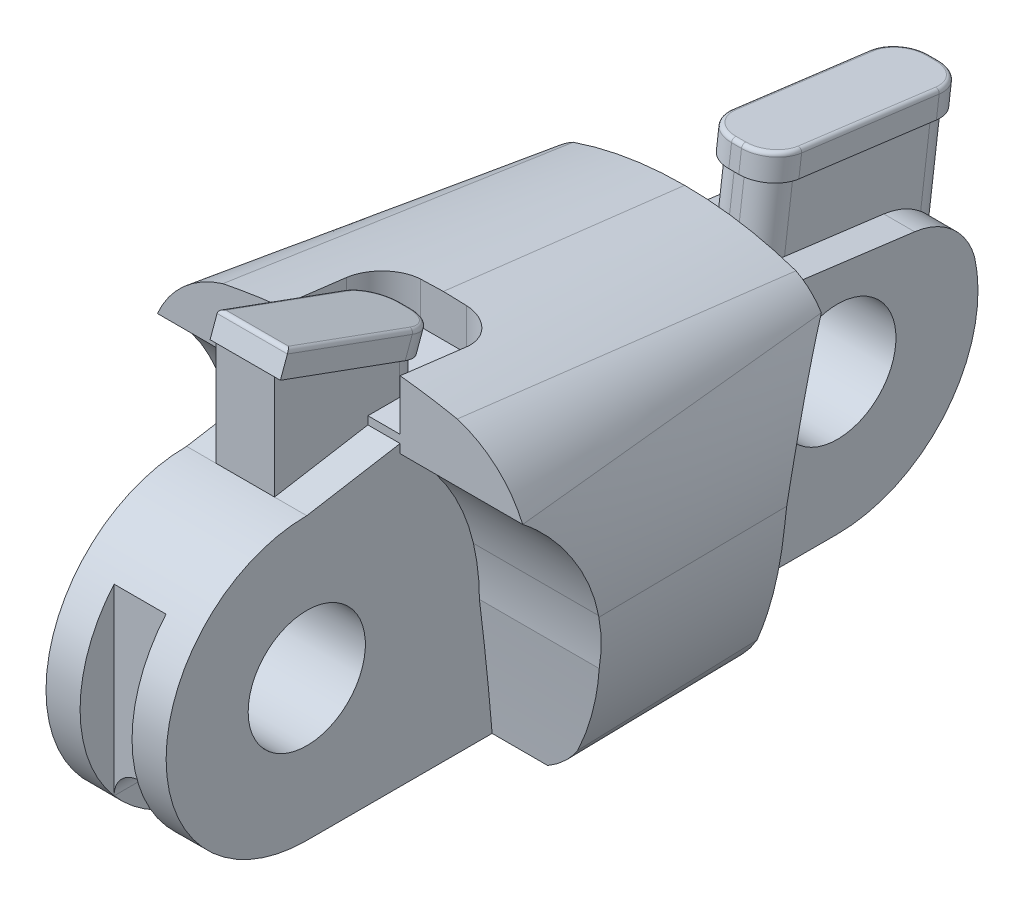
SolidWorks part; units mm, degrees
material "PET"
ref_plane "Front Plane" through (0, 0, 0) normal (0, 0, 1) x (1, 0, 0)
ref_plane "Top Plane" through (0, 0, 0) normal (0, 1, 0) x (1, 0, 0)
ref_plane "Right Plane" through (0, 0, 0) normal (1, 0, 0) x (0, 0, -1)
sketch "Sketch1" plane through (0, 0, 0) normal (1, 0, 0) x (0, 0, -1)
  line L0 (-17.2498, 0) -> (17.2498, 0) construction
  line L1 (-17.2498, 9.144) -> (17.2498, 9.144)
  line L2 (-17.2498, -9.144) -> (17.2498, -9.144)
  arc A0 (-17.2498, 9.144) -> (-17.2498, -9.144) centre (-17.2498, 0) ccw
  arc A1 (17.2498, -9.144) -> (17.2498, 9.144) centre (17.2498, 0) ccw
  circle A2 centre (-17.2498, 0) radius 3.81
  circle A3 centre (17.2498, 0) radius 3.81
  point P3 (0, 0)
  dimension "D2" = 9.144
  dimension "D3" = 7.62
  dimension "D1" = 34.4995
extrude "Boss-Extrude1" add sketch "Sketch1" along normal mid plane 7.8105
ref_plane "Plane1" through (0, 0, 11.1792) normal (0, 0, 1) x (1, 0, 0)
ref_plane "Plane2" through (0, 0, -11.2236) normal (0, 0, 1) x (1, 0, 0)
sketch "Sketch2" plane through (0, 0, 11.1792) normal (0, 0, 1) x (1, 0, 0)
  line L0 (0, -9.144) -> (0, 13.716) construction
  line L1 (3.9052, -9.144) -> (-3.9052, -9.144) construction
  line L2 (3.9053, 13.716) -> (-3.9053, 13.716) construction
  line L3 (7.62, -9.144) -> (-7.62, -9.144)
  line L4 (0, 2.286) -> (-12.319, 2.286) construction
  line L5 (0, 9.6012) -> (-11.8745, 9.6012) construction
  line L6 (-3.9052, 9.144) -> (-3.9052, -9.144) construction
  arc A0 (-7.62, -9.144) -> (-9.652, -7.3279) centre (-4.2348, -3.3115) cw
  arc A1 (-12.319, 2.286) -> (-9.652, -7.3279) centre (9.1301, 3.0593) ccw
  arc A2 (-12.319, 2.286) -> (-11.8745, 9.6012) centre (16.3435, 4.2155) cw
  arc A3 (-11.8745, 9.6012) -> (-7.62, 13.4112) centre (-5.6343, 6.9134) cw
  arc A4 (-7.62, 13.4112) -> (0, 14.224) centre (0.4948, -26.54) cw
  arc A5 (7.62, -9.144) -> (9.652, -7.3279) centre (4.2348, -3.3115) ccw
  arc A6 (12.319, 2.286) -> (9.652, -7.3279) centre (-9.1301, 3.0593) cw
  arc A7 (12.319, 2.286) -> (11.8745, 9.6012) centre (-16.3435, 4.2155) ccw
  arc A8 (11.8745, 9.6012) -> (7.62, 13.4112) centre (5.6343, 6.9134) ccw
  arc A9 (7.62, 13.4112) -> (0, 14.224) centre (-0.4948, -26.54) ccw
  dimension "D6" = 6.7437
  dimension "D9" = 21.463
  dimension "D10" = 28.7274
  dimension "D12" = 6.7945
  dimension "D14" = 40.767
  dimension "D1" = 22.86
  dimension "D2" = 7.62
  dimension "D3" = 12.319
  dimension "D4" = 11.8745
  dimension "D5" = 7.3152
  dimension "D7" = 2.032
  dimension "D8" = 1.8161
  dimension "D11" = 3.81
  dimension "D13" = 0.508
sketch "Sketch3" plane through (0, 0, -11.2236) normal (0, 0, 1) x (1, 0, 0)
  line L0 (0, -9.144) -> (0, 11.557) construction
  line L1 (3.9052, -9.144) -> (-3.9052, -9.144) construction
  line L2 (7.239, -9.144) -> (-7.239, -9.144)
  line L3 (0, 1.2065) -> (-10.9855, 1.2065) construction
  line L4 (0, 8.8265) -> (-8.89, 8.8265) construction
  line L5 (164.5619, 543.9025) -> (873.8952, 543.9025) construction
  arc A0 (-7.239, -9.144) -> (-9.6266, -6.604) centre (-3.4088, -3.1515) cw
  arc A1 (-9.6266, -6.604) -> (-10.9855, 1.2065) centre (7.283, 0.3615) cw
  arc A2 (-10.9855, 1.2065) -> (-8.89, 8.8265) centre (3.2373, 1.3934) cw
  arc A3 (-8.89, 8.8265) -> (-7.239, 10.3632) centre (-5.303, 6.6279) cw
  arc A4 (-7.239, 10.3632) -> (0, 11.557) centre (-0.0528, -10.6679) cw
  arc A5 (7.239, -9.144) -> (9.6266, -6.604) centre (3.4088, -3.1515) ccw
  arc A6 (9.6266, -6.604) -> (10.9855, 1.2065) centre (-7.283, 0.3615) ccw
  arc A7 (10.9855, 1.2065) -> (8.89, 8.8265) centre (-3.2373, 1.3934) ccw
  arc A8 (8.89, 8.8265) -> (7.239, 10.3632) centre (5.303, 6.6279) ccw
  arc A9 (7.239, 10.3632) -> (0, 11.557) centre (0.0528, -10.6679) ccw
  point P10 (0, 1.2065)
  dimension "D6" = 7.112
  dimension "D9" = 18.288
  dimension "D10" = 14.224
  dimension "D12" = 22.225
  dimension "D1" = 20.701
  dimension "D2" = 7.239
  dimension "D3" = 10.9855
  dimension "D4" = 8.89
  dimension "D5" = 7.62
  dimension "D7" = 2.54
  dimension "D8" = 2.3876
  dimension "D11" = 1.5367
loft "Loft1" add profiles "Sketch2", "Sketch3" connector at (0, 14.224, 11.1792) connector at (0, 11.557, -11.2236)
sketch "Sketch5" plane through (-3.9052, 0, 0) normal (-1, 0, 0) x (0, 0, 1)
  line L0 (11.1792, 9.6012) -> (11.1792, -9.144)
  line L1 (17.2498, -9.144) -> (-17.2498, -9.144) construction
  line L2 (11.1792, -9.144) -> (5.1975, -9.144)
  line L3 (11.1792, -9.144) -> (-11.2236, -9.144) construction
  line L4 (11.1792, 2.286) -> (11.1792, 9.6012) construction
  line L5 (-11.2236, 8.8265) -> (-11.2236, -9.144)
  line L6 (-11.2236, -9.144) -> (-6.4611, -9.144)
  line L7 (91.3421, 313.5507) -> (503.3421, 313.5507) construction
  arc A0 (11.1792, 9.6012) -> (6.4141, 2.1704) centre (19.294, -0.8457) ccw
  arc A1 (6.4141, 2.1704) -> (6.023, -1.1824) centre (20.8747, -1.2159) ccw
  arc A2 (5.1975, -9.144) -> (6.023, -1.1824) centre (199.298, -25.2457) cw
  arc A3 (-11.2236, 8.8265) -> (-6.4611, 0.4026) centre (-18.1635, -0.6552) cw
  arc A4 (-6.4611, 0.4026) -> (-6.4611, -9.144) centre (-59.2693, -4.3707) cw
  dimension "D3" = 13.2283
  dimension "D8" = 194.7672
  dimension "D9" = 11.75
  dimension "D1" = 5.9817
  dimension "D2" = 4.7625
  dimension "D4" = 4.765
  dimension "D5" = 7.4308
  dimension "D6" = 5.1562
  dimension "D7" = 3.3528
  dimension "D10" = 8.4239
extrude "Cut-Extrude1" cut sketch "Sketch5" along normal blind 10.16
mirror "Mirror1" about plane through (0, 0, 0) normal (1, 0, 0) of "Cut-Extrude1"
sketch "Sketch6" plane through (-3.9052, 0, 0) normal (-1, 0, 0) x (0, 0, 1)
  line L0 (-11.2236, 11.5571) -> (-11.2236, -9.144) construction
  line L1 (17.2498, -9.144) -> (-17.2498, -9.144) construction
  line L2 (-11.2236, 8.8265) -> (-11.2236, -9.144) construction
  line L3 (0, 0) -> (-26.3938, 0) construction
  line L4 (54.4978, 392.9909) -> (430.4978, 392.9909) construction
  line L5 (141.4324, 674.1494) -> (813.4324, 674.1494) construction
  line L6 (-11.2236, 11.5571) -> (-11.2236, 2.0067) construction
  line L7 (-11.2236, 2.0067) -> (-26.1709, 2.0067) construction
  line L8 (-11.2236, 6.7946) -> (-22.2726, 5.3713)
  line L9 (-26.1709, 2.0067) -> (-26.1709, 11.5571)
  line L10 (-26.1709, 11.5571) -> (-11.2236, 11.5571)
  line L11 (-11.2236, 11.5571) -> (-11.2236, 6.7946)
  arc A0 (-17.2498, 9.144) -> (-17.2498, -9.144) centre (-17.2498, 0) ccw construction
  arc A1 (-26.1709, 2.0067) -> (-22.2726, 5.3713) centre (-21.676, 0.7395) cw
  dimension "D1" = 9.5504
  dimension "D2" = 4.7879
  dimension "D3" = 97.34
  dimension "D4" = 11.049
extrude "Cut-Extrude2" cut sketch "Sketch6" against normal up to surface (7.8105 mm away) up to face at (3.9052, 0, 13.4398)
sketch "Sketch7" plane through (0, 9.144, 0) normal (0, 1, 0) x (1, 0, 0)
  line L0 (-3.9052, -11.1792) -> (3.9052, -11.1792)
  line L1 (-3.9052, 11.2236) -> (-3.9052, -17.2498) construction
  line L2 (3.9052, 11.2236) -> (3.9052, -17.2498) construction
  line L3 (-3.9052, -11.1792) -> (-3.9053, -6.8612)
  line L4 (-1.4986, -4.4609) -> (1.4986, -4.4609)
  line L5 (0, -4.4609) -> (0, -11.1792) construction
  line L6 (3.9052, -11.1792) -> (3.9053, -6.8612)
  arc A0 (-3.9053, -6.8612) -> (-1.4986, -4.4609) centre (-1.5049, -6.8612) cw
  arc A1 (3.9053, -6.8612) -> (1.4986, -4.4609) centre (1.5049, -6.8612) ccw
  dimension "D1" = 2.9972
  dimension "D2" = 4.318
  dimension "D3" = 2.4003
extrude "Cut-Extrude3" cut sketch "Sketch7" along normal blind 5.08 from offset 1.545
sketch "Sketch8" plane through (-3.9052, 0, 0) normal (-1, 0, 0) x (0, 0, 1)
  line L0 (11.1792, 9.6012) -> (11.1792, 10.1727) construction
  line L1 (11.1792, 9.6012) -> (11.1792, 13.4112) construction
  line L2 (11.1792, 9.144) -> (17.2498, 9.144)
  line L3 (11.1792, -9.144) -> (11.1792, 9.6012) construction
  line L4 (-11.2236, 9.144) -> (17.2498, 9.144) construction
  line L5 (17.2498, 9.144) -> (11.1792, 10.1727)
  line L6 (11.1792, 9.144) -> (11.1792, 10.1727)
  dimension "D1" = 0.5715
extrude "Boss-Extrude2" add sketch "Sketch8" against normal up to surface (7.8105 mm away) up to face at (3.9052, 1.8021, -6.8117)
sketch "Sketch9" plane through (-3.9052, 0, 0) normal (-1, 0, 0) x (0, 0, 1)
  line L0 (17.2498, 9.144) -> (-1.3412, 9.144) construction
  line L1 (17.2498, 9.144) -> (11.1792, 10.1727) construction
  line L2 (-1.3412, 9.144) -> (17.2498, 15.9106) construction
  line L3 (17.2498, 15.9106) -> (17.2498, 9.144) construction
  line L4 (78.3172, 279.9032) -> (347.6505, 279.9032) construction
  line L5 (17.2498, 9.144) -> (17.2498, 15.9106)
  line L6 (17.2498, 15.9106) -> (-1.3412, 9.144)
  line L7 (-1.3412, 9.144) -> (17.2498, 9.144)
  arc A0 (17.2498, -9.144) -> (17.2498, 9.144) centre (17.2498, 0) ccw construction
  dimension "D1" = 6.7666
  dimension "D2" = 20
extrude "Boss-Extrude3" add sketch "Sketch9" against normal blind 3.81 from offset 1.905 offset against normal yes
sketch "Sketch10" plane through (0, 8.5054, -3.0957) normal (0, 0.9397, -0.342) x (1, 0, 0)
  line L0 (-2.0003, -21.6512) -> (1.8097, -21.6512)
  line L1 (1.8097, -21.6512) -> (-2.0003, -21.6512) construction
  line L2 (1.8097, -21.6512) -> (1.8097, -13.0152)
  line L3 (1.8097, -13.9843) -> (1.8097, -19.3369) construction
  line L4 (0.2286, -11.4341) -> (-0.4191, -11.4341)
  line L5 (-0.0953, -11.4341) -> (-0.0953, -21.6512) construction
  line L6 (-2.0003, -21.6512) -> (-2.0003, -13.0152)
  arc A0 (1.8097, -13.0152) -> (0.2286, -11.4341) centre (0.2286, -13.0152) ccw
  arc A1 (-2.0003, -13.0152) -> (-0.4191, -11.4341) centre (-0.4191, -13.0152) cw
  dimension "D1" = 8.636
  dimension "D2" = 0.6477
sketch "Sketch11" plane through (0, 10.689, 0) normal (0, 1, 0) x (1, 0, 0)
  line L0 (-2.0003, -9.1346) -> (-3.9053, -9.1346)
  line L1 (-1.4986, -4.4609) -> (1.4986, -4.4609)
  line L2 (1.8097, -9.1346) -> (3.9053, -9.1346)
  line L3 (3.9053, -6.8612) -> (3.9052, -11.1792) construction
  line L4 (-3.9052, -11.1792) -> (-3.9053, -6.8612) construction
  line L5 (-3.9053, -9.1346) -> (-3.9053, -6.8612)
  line L6 (3.9053, -9.1346) -> (3.9053, -6.8612)
  line L7 (-0.4191, -7.6488) -> (0.2286, -7.6488)
  arc A0 (-3.9053, -6.8612) -> (-1.4986, -4.4609) centre (-1.4986, -6.8675) cw
  arc A1 (3.9053, -6.8612) -> (1.4986, -4.4609) centre (1.5049, -6.8612) ccw
  arc A2 (-2.0003, -9.1346) -> (-0.4191, -7.6488) centre (-0.5116, -9.1346) cw
  arc A3 (0.2286, -7.6488) -> (1.8097, -9.1346) centre (0.2286, -9.233) cw
extrude "Cut-Extrude4" cut sketch "Sketch11" along normal up to vertex (2.7352 mm away) up to point (0, 13.4242, 4.4609)
sketch "Sketch12" plane through (0, 8.5054, -3.0957) normal (0, 0.9397, -0.342) x (1, 0, 0)
  line L0 (1.8097, -21.6512) -> (2.1907, -21.6512)
  line L1 (2.1907, -21.6512) -> (2.1907, -13.0152)
  line L2 (0.2286, -11.0531) -> (-0.4191, -11.0531)
  line L3 (-2.3813, -13.0152) -> (-2.3813, -21.6512)
  line L4 (-2.3813, -21.6512) -> (-2.0003, -21.6512)
  line L5 (-2.0003, -21.6512) -> (1.8097, -21.6512) construction
  line L6 (1.8097, -21.6512) -> (1.8097, -13.0152) construction
  line L7 (0.2286, -11.4341) -> (-0.4191, -11.4341) construction
  line L8 (-2.0003, -21.6512) -> (-2.0003, -13.0152) construction
  line L9 (-2.0003, -21.6512) -> (1.8097, -21.6512)
  arc A0 (2.1907, -13.0152) -> (0.2286, -11.0531) centre (0.2286, -13.0152) ccw
  arc A1 (-0.4191, -11.0531) -> (-2.3813, -13.0152) centre (-0.4191, -13.0152) ccw
  dimension "D1" = 0.381
  dimension "D2" = 0.381
extrude "Boss-Extrude5" add sketch "Sketch12" along normal blind 1.585
sketch "Sketch13" plane through (0, 8.1058, -1.0441) normal (0, 0.9918, -0.1278) x (1, 0, 0)
  line L0 (0, 10.2636) -> (0, 13.3116) construction
  line L1 (3.9052, 10.2636) -> (-3.9052, 10.2636) construction
  line L2 (-0.3238, 13.3116) -> (0.3238, 13.3116)
  line L3 (1.905, 14.8927) -> (1.905, 23.9097)
  line L4 (1.905, 19.4012) -> (0, 19.4012) construction
  line L5 (0, 13.3116) -> (0, 19.4012) construction
  line L6 (-0.3238, 25.4909) -> (0.3239, 25.4909)
  line L7 (-1.905, 14.8927) -> (-1.905, 23.9097)
  arc A0 (0.3238, 13.3116) -> (1.905, 14.8927) centre (0.3238, 14.8927) ccw
  arc A1 (0.3239, 25.4909) -> (1.905, 23.9097) centre (0.3239, 23.9097) cw
  arc A2 (-0.3238, 25.4909) -> (-1.905, 23.9097) centre (-0.3239, 23.9097) ccw
  arc A3 (-0.3238, 13.3116) -> (-1.905, 14.8927) centre (-0.3238, 14.8927) cw
  point P7 (0, 13.3116)
  dimension "D1" = 3.048
  dimension "D2" = 0.6477
  dimension "D3" = 9.017
  dimension "D4" = 1.905
extrude "Boss-Extrude6" add sketch "Sketch13" along normal blind 6.223 from offset 1.905 offset against normal yes
sketch "Sketch14" plane through (0, 12.3884, -1.5958) normal (0, 0.9918, -0.1278) x (1, 0, 0)
  line L0 (0.3238, 12.9306) -> (-0.3239, 12.9306)
  line L1 (-0.3238, 13.3116) -> (0.3238, 13.3116) construction
  line L2 (2.286, 14.8927) -> (2.286, 23.9097)
  line L3 (1.905, 14.8927) -> (1.905, 23.9097) construction
  line L4 (0, 12.9306) -> (0, 19.4012) construction
  line L5 (0, 19.4012) -> (2.286, 19.4012) construction
  line L6 (0.3238, 25.8719) -> (-0.3239, 25.8719)
  line L7 (-2.286, 14.8927) -> (-2.286, 23.9097)
  arc A0 (0.3238, 12.9306) -> (2.286, 14.8927) centre (0.3238, 14.8927) ccw
  arc A1 (0.3238, 25.8719) -> (2.286, 23.9097) centre (0.3238, 23.9097) cw
  arc A2 (-0.3239, 25.8719) -> (-2.286, 23.9097) centre (-0.3238, 23.9097) ccw
  arc A3 (-0.3239, 12.9306) -> (-2.286, 14.8927) centre (-0.3239, 14.8927) cw
  point P7 (0, 12.9306)
  dimension "D1" = 0.381
  dimension "D2" = 0.381
extrude "Boss-Extrude7" add sketch "Sketch14" along normal blind 1.6383
fillet "Fillet1" radius 0.254 14 edges at (0, 12.3613, -14.6297) (-1.7113, 12.2879, -15.1997) (-2.286, 11.5347, -21.0474) (-1.7113, 10.7814, -26.895) (0, 10.708, -27.465) (1.7113, 10.7814, -26.895) (2.286, 11.5347, -21.0474) (1.7113, 12.2879, -15.1997) (-2.3813, 15.9231, 12.6501) (-1.8065, 13.9717, 7.2887) (-0.0953, 13.7752, 6.7487) (1.616, 13.9717, 7.2887) (2.1907, 15.9231, 12.6501) (-0.0953, 17.3999, 16.7077)
sketch "Sketch16" plane through (0, -9.144, 0) normal (0, -1, 0) x (1, 0, 0)
  line L0 (0, 0) -> (0, 26.3938) construction
  line L1 (3.9052, 26.3938) -> (-3.9052, 26.3938) construction
  line L2 (3.9053, 26.3938) -> (-3.9052, 26.3938) construction
  line L3 (-3.9052, 26.3938) -> (-3.9052, 17.2498) construction
  line L5 (-1.6891, 26.3938) -> (1.6891, 26.3938)
  line L6 (-1.6891, 26.3938) -> (-1.6891, 24.184)
  line L7 (-1.6891, 24.184) -> (1.6891, 24.184)
  line L8 (1.6891, 26.3938) -> (1.6891, 24.184)
  line L9 (-1.6891, 26.3938) -> (1.6891, 24.184) construction
  line L10 (-1.6891, 24.184) -> (1.6891, 26.3938) construction
  point P13 (0, 26.3938)
  point P14 (0, 25.2889)
  dimension "D1" = 3.3782
  dimension "D2" = 2.2098
extrude "Cut-Extrude5" cut sketch "Sketch16" against normal up to vertex (18.288 mm away) up to point (3.9053, 9.144, 17.2498)
sketch "Sketch17" plane through (0, 0, 24.184) normal (0, 0, 1) x (1, 0, 0)
  line L0 (3.9052, -9.144) -> (-3.9052, -9.144) construction
  line L1 (-1.6891, -5.9607) -> (1.6891, -5.9607) construction
  line L2 (-1.6891, -5.9607) -> (-1.6891, -9.144)
  line L3 (-1.6891, -9.144) -> (1.6891, -9.144)
  line L4 (1.6891, -5.9607) -> (1.6891, -9.144)
  arc A0 (1.6891, -5.9607) -> (-1.6891, -5.9607) centre (0, -5.9607) ccw
extrude "Cut-Extrude6" cut sketch "Sketch17" against normal up to vertex (17.7698 mm away) up to point (-12.0414, 2.1704, 6.4141)
mirror "Mirror2" about plane through (0, 0, 0) normal (0, 0, 1) of "Cut-Extrude6"
sketch "Sketch18" plane through (0, 0, 6.4141) normal (0, 0, 1) x (1, 0, 0)
  circle A0 centre (0, -5.9607) radius 1.6891
  arc A2 (1.6891, -5.9607) -> (-1.6891, -5.9607) centre (0, -5.9607) ccw construction
extrude "Cut-Extrude7" cut sketch "Sketch18" against normal through all
